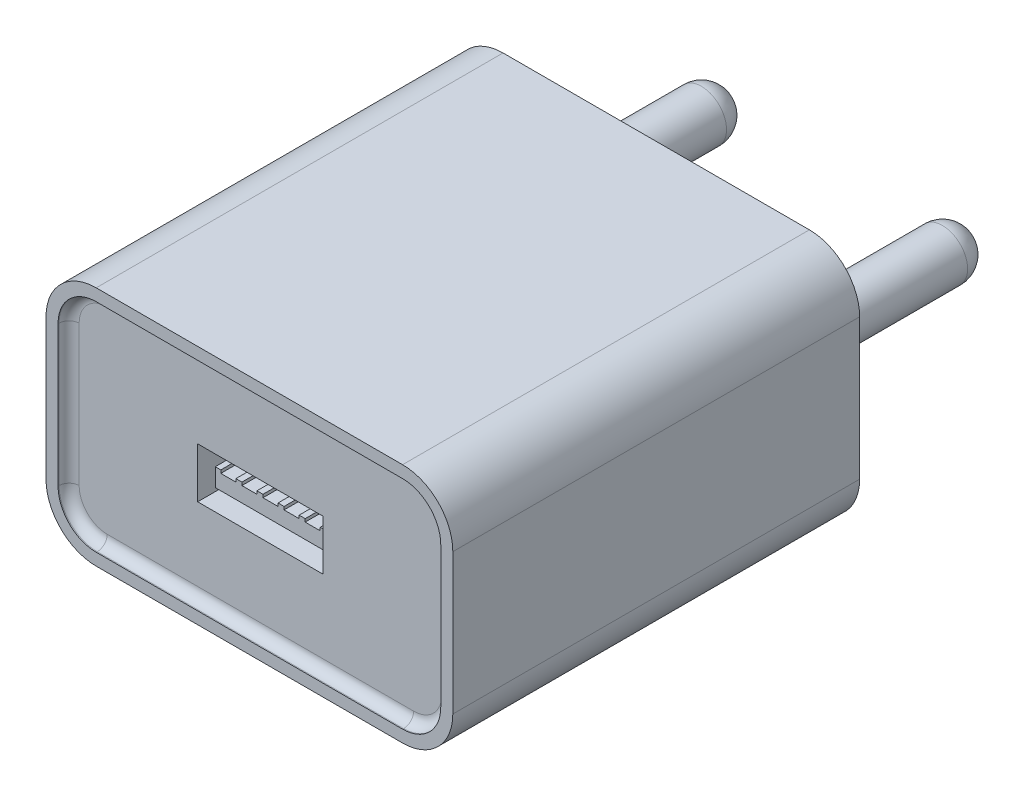
SolidWorks part; units mm, degrees
ref_plane "Front Plane" through (0, 0, 0) normal (0, 0, 1) x (1, 0, 0)
ref_plane "Top Plane" through (0, 0, 0) normal (0, 1, 0) x (1, 0, 0)
ref_plane "Right Plane" through (0, 0, 0) normal (1, 0, 0) x (0, 0, -1)
sketch "Sketch1" plane through (0, 0, 0) normal (0, 0, 1) x (1, 0, 0)
  line L1 (-20.25, 12) -> (20.25, 12)
  line L2 (-20.25, 12) -> (-20.25, -12)
  line L3 (-20.25, -12) -> (20.25, -12)
  line L4 (20.25, 12) -> (20.25, -12)
  line L5 (-20.25, 12) -> (20.25, -12) construction
  line L6 (-20.25, -12) -> (20.25, 12) construction
  point P0 (0, 0)
  dimension "D1" = 40.5
  dimension "D2" = 24
extrude "Boss-Extrude1" add sketch "Sketch1" along normal mid plane 40.5
fillet "Fillet1" radius 5 4 edges at (20.25, -12, 0) (-20.25, -12, 0) (20.25, 12, 0) (-20.25, 12, 0)
sketch "Sketch13" plane through (0, 0, 20.25) normal (0, 0, 1) x (1, 0, 0)
  line L4 (-15.25, -12) -> (15.25, -12)
  line L5 (20.25, -7) -> (20.25, 7)
  line L6 (15.25, 12) -> (-15.25, 12)
  line L7 (-20.25, 7) -> (-20.25, -7)
  line L8 (-15.25, -12) -> (15.25, -12)
  line L9 (20.25, -7) -> (20.25, 7)
  line L10 (15.25, 12) -> (-15.25, 12)
  line L11 (-20.25, 7) -> (-20.25, -7)
  line L28 (-15.25, -12) -> (15.25, -12) construction
  line L29 (20.25, -7) -> (20.25, 7) construction
  line L30 (15.25, 12) -> (-15.25, 12) construction
  line L31 (-20.25, 7) -> (-20.25, -7) construction
  line L32 (20.25, 7) -> (20.25, -7) construction
  line L33 (15.25, -12) -> (-15.25, -12) construction
  line L34 (-20.25, -7) -> (-20.25, 7) construction
  line L35 (-15.25, 12) -> (15.25, 12) construction
  line L36 (-15.25, -12) -> (15.25, -12)
  line L37 (20.25, -7) -> (20.25, 7)
  line L38 (15.25, 12) -> (-15.25, 12)
  line L39 (-20.25, 7) -> (-20.25, -7)
  line L40 (20.25, 7) -> (20.25, -7)
  line L41 (15.25, -12) -> (-15.25, -12)
  line L42 (-20.25, -7) -> (-20.25, 7)
  line L43 (-15.25, 12) -> (15.25, 12)
  line L52 (-15.25, -10.8) -> (15.25, -10.8)
  line L53 (19.05, -7) -> (19.05, 7)
  line L54 (15.25, 10.8) -> (-15.25, 10.8)
  line L55 (-19.05, 7) -> (-19.05, -7)
  line L56 (-15.25, -10.8) -> (15.25, -10.8)
  line L57 (19.05, -7) -> (19.05, 7)
  line L58 (15.25, 10.8) -> (-15.25, 10.8)
  line L59 (-19.05, 7) -> (-19.05, -7)
  arc A4 (15.25, -12) -> (20.25, -7) centre (15.25, -7) ccw
  arc A5 (20.25, 7) -> (15.25, 12) centre (15.25, 7) ccw
  arc A6 (-15.25, 12) -> (-20.25, 7) centre (-15.25, 7) ccw
  arc A7 (-20.25, -7) -> (-15.25, -12) centre (-15.25, -7) ccw
  arc A8 (15.25, -12) -> (20.25, -7) centre (15.25, -7) ccw
  arc A9 (20.25, 7) -> (15.25, 12) centre (15.25, 7) ccw
  arc A10 (-15.25, 12) -> (-20.25, 7) centre (-15.25, 7) ccw
  arc A11 (-20.25, -7) -> (-15.25, -12) centre (-15.25, -7) ccw
  arc A28 (15.25, -12) -> (20.25, -7) centre (15.25, -7) ccw construction
  arc A29 (20.25, 7) -> (15.25, 12) centre (15.25, 7) ccw construction
  arc A30 (-15.25, 12) -> (-20.25, 7) centre (-15.25, 7) ccw construction
  arc A31 (-20.25, -7) -> (-15.25, -12) centre (-15.25, -7) ccw construction
  arc A32 (15.25, -12) -> (20.25, -7) centre (15.25, -7) ccw construction
  arc A33 (-20.25, -7) -> (-15.25, -12) centre (-15.25, -7) ccw construction
  arc A34 (-15.25, 12) -> (-20.25, 7) centre (-15.25, 7) ccw construction
  arc A35 (20.25, 7) -> (15.25, 12) centre (15.25, 7) ccw construction
  arc A36 (15.25, -12) -> (20.25, -7) centre (15.25, -7) ccw
  arc A37 (20.25, 7) -> (15.25, 12) centre (15.25, 7) ccw
  arc A38 (-15.25, 12) -> (-20.25, 7) centre (-15.25, 7) ccw
  arc A39 (-20.25, -7) -> (-15.25, -12) centre (-15.25, -7) ccw
  arc A40 (15.25, -12) -> (20.25, -7) centre (15.25, -7) ccw
  arc A41 (-20.25, -7) -> (-15.25, -12) centre (-15.25, -7) ccw
  arc A42 (-15.25, 12) -> (-20.25, 7) centre (-15.25, 7) ccw
  arc A43 (20.25, 7) -> (15.25, 12) centre (15.25, 7) ccw
  arc A52 (15.25, -10.8) -> (19.05, -7) centre (15.25, -7) ccw
  arc A53 (19.05, 7) -> (15.25, 10.8) centre (15.25, 7) ccw
  arc A54 (-15.25, 10.8) -> (-19.05, 7) centre (-15.25, 7) ccw
  arc A55 (-19.05, -7) -> (-15.25, -10.8) centre (-15.25, -7) ccw
  arc A56 (15.25, -10.8) -> (19.05, -7) centre (15.25, -7) ccw
  arc A57 (19.05, 7) -> (15.25, 10.8) centre (15.25, 7) ccw
  arc A58 (-15.25, 10.8) -> (-19.05, 7) centre (-15.25, 7) ccw
  arc A59 (-19.05, -7) -> (-15.25, -10.8) centre (-15.25, -7) ccw
  dimension "D1" = 0
  dimension "D2" = 1.2
extrude "Cut-Extrude7" cut sketch "Sketch13" against normal blind 1.1 contours L59 A59 L56 A56 L57 A57 L58 A58 region at (0, 0, 20.25)
fillet "Fillet2" radius 1 8 edges at (-17.937, 9.687, 19.15) (0, 10.8, 19.15) (17.937, 9.687, 19.15) (19.05, 0, 19.15) (17.937, -9.687, 19.15) (0, -10.8, 19.15) (-17.937, -9.687, 19.15) (-19.05, 0, 19.15)
sketch "Sketch14" plane through (0, 0, -20.25) normal (0, 0, -1) x (-1, 0, 0)
  circle A0 centre (-12, 0) radius 2.5
  circle A1 centre (12, 0) radius 2.5
  dimension "D1" = 5
  dimension "D2" = 12
  dimension "D3" = 12
extrude "Boss-Extrude3" add sketch "Sketch14" along normal blind 16.5 contours A1 | A0
dome "Dome1" faces to dome 1 distance 2.5 reverse direction no elliptical dome no face at (9.5, 0, -36.75) parameters "D1"=2.5
dome "Dome2" faces to dome 1 distance 2.5 reverse direction no elliptical dome no face at (-14.5, 0, -36.75) parameters "D1"=2.5
sketch "Sketch15" plane through (0, 0, 19.15) normal (0, 0, 1) x (1, 0, 0)
  line L1 (-6.25, 2.5) -> (6.25, 2.5)
  line L2 (-6.25, 2.5) -> (-6.25, -2.5)
  line L3 (-6.25, -2.5) -> (6.25, -2.5)
  line L4 (6.25, 2.5) -> (6.25, -2.5)
  line L5 (-6.25, 2.5) -> (6.25, -2.5) construction
  line L6 (-6.25, -2.5) -> (6.25, 2.5) construction
  point P0 (0, 0)
  dimension "D1" = 12.5
  dimension "D2" = 5
extrude "Cut-Extrude8" cut sketch "Sketch15" against normal blind 12
sketch "Sketch17" plane through (0, 0, 7.15) normal (0, 0, 1) x (1, 0, 0)
  line L0 (6.25, 2.5) -> (-6.25, 2.5) construction
  line L1 (-5.5, 0.4) -> (5.5, 0.4)
  line L2 (-5.5, 0.4) -> (-5.5, -1.4)
  line L3 (-5.5, -1.4) -> (5.5, -1.4)
  line L4 (5.5, 0.4) -> (5.5, -1.4)
  line L5 (-5.5, 0.4) -> (5.5, -1.4) construction
  line L6 (-5.5, -1.4) -> (5.5, 0.4) construction
  point P0 (0, -0.5)
  dimension "D1" = 11
  dimension "D2" = 1.8
  dimension "D3" = 2.1
extrude "Boss-Extrude4" add sketch "Sketch17" along normal blind 11
sketch "Sketch18" plane through (0, 0, 18.15) normal (0, 0, 1) x (1, 0, 0)
  line L0 (-5.5, -1.4) -> (5.5, -1.4) construction
  line L1 (-0.75, 0.5) -> (0.75, 0.5)
  line L2 (-0.75, 0.5) -> (-0.75, 0.1)
  line L3 (-0.75, 0.1) -> (0.75, 0.1)
  line L4 (0.75, 0.5) -> (0.75, 0.1)
  line L5 (-0.75, 0.5) -> (0.75, 0.1) construction
  line L6 (-0.75, 0.1) -> (0.75, 0.5) construction
  point P0 (0, 0.3)
  dimension "D1" = 1.5
  dimension "D2" = 0.4
  dimension "D3" = 1.5
extrude "Cut-Extrude9" cut sketch "Sketch18" against normal blind 2
pattern_linear "LPattern1" count 3 spacing 2.1 along (1, 0, 0) count 3 spacing 2.1 along (-1, 0, 0) of "Cut-Extrude9"
